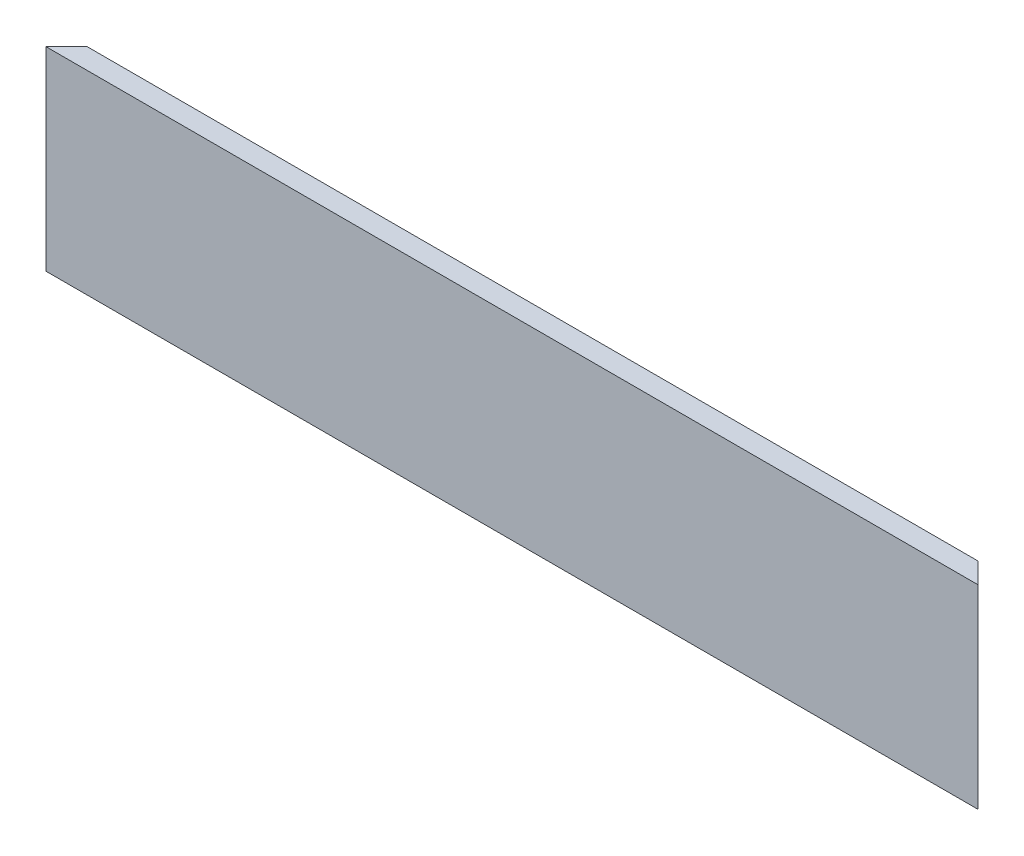
SolidWorks part; units mm, degrees
ref_plane "Front Plane" through (0, 0, 0) normal (0, 0, 1) x (1, 0, 0)
ref_plane "Top Plane" through (0, 0, 0) normal (0, 1, 0) x (1, 0, 0)
ref_plane "Right Plane" through (0, 0, 0) normal (1, 0, 0) x (0, 0, -1)
sketch "Sketch1" plane through (0, 0, 0) normal (0, 0, 1) x (1, 0, 0)
  line L1 (287.5, -60) -> (-287.5, -60)
  line L2 (287.5, -60) -> (287.5, 60)
  line L3 (287.5, 60) -> (-287.5, 60)
  line L4 (-287.5, -60) -> (-287.5, 60)
  line L5 (287.5, -60) -> (-287.5, 60) construction
  line L6 (287.5, 60) -> (-287.5, -60) construction
  point P0 (0, 0)
  dimension "D1" = 120
  dimension "D2" = 575
extrude "Boss-Extrude1" add sketch "Sketch1" along normal blind 12.7
chamfer "Chamfer1" distance 12.7 angle 45 3 edges at (287.5, 0, 0) (0, -60, 0) (-287.5, 0, 0)
